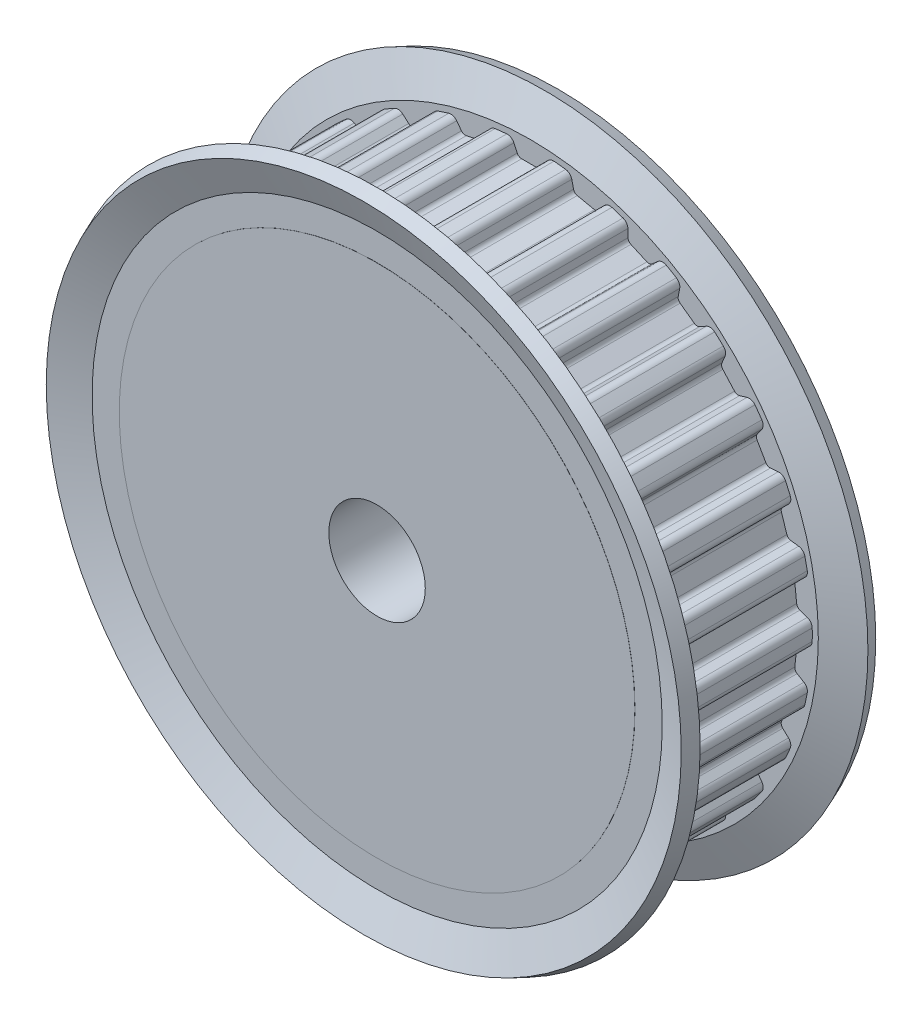
SolidWorks part; units mm, degrees
ref_plane "Front Plane" through (0, 0, 0) normal (0, 0, 1) x (1, 0, 0)
ref_plane "Top Plane" through (0, 0, 0) normal (0, 1, 0) x (1, 0, 0)
ref_plane "Right Plane" through (0, 0, 0) normal (1, 0, 0) x (0, 0, -1)
ref_axis "Axis1" through (0, 0, 55) along (0, 0, -1)
sketch "SketchRevolveGearBelt01" plane through (0, 0, 0) normal (1, 0, 0) x (0, 0, -1)
  line L0 (0, 0) -> (1, 0) construction
  line L1 (6.96, 0) -> (6.96, 21.3732)
  line L2 (6.96, 21.3732) -> (6.95, 21.3732)
  line L3 (6.95, 21.3732) -> (6.95, 23.6345)
  line L4 (6.95, 23.6345) -> (8.0633, 26.3223)
  line L5 (8.0633, 26.3223) -> (6.9547, 26.7815)
  line L6 (6.9547, 26.7815) -> (5.75, 23.8732)
  line L7 (5.75, 23.8732) -> (5.75, 23.3732)
  line L8 (5.75, 23.3732) -> (-5.75, 23.3732)
  line L9 (-5.75, 23.3732) -> (-5.75, 23.8732)
  line L10 (-5.75, 23.8732) -> (-6.9547, 26.7815)
  line L11 (-6.9547, 26.7815) -> (-8.0633, 26.3223)
  line L12 (-8.0633, 26.3223) -> (-6.95, 23.6345)
  line L13 (-6.95, 23.6345) -> (-6.95, 21.3732)
  line L14 (-6.95, 21.3732) -> (-6.96, 21.3732)
  line L15 (-6.96, 21.3732) -> (-6.96, 0)
  line L16 (-6.96, 0) -> (6.96, 0)
  dimension "GearBeltSide1" = 6.96
  dimension "GearBeltFlange1OutsideWidth" = 6.95
  dimension "GearBeltFlange1OutsideLength" = 2.2613
  dimension "GearBeltFlange1X" = 1.1133
  dimension "GearBeltFlange1Y" = 2.6878
  dimension "GearBeltFlangeThickness" = 1.2
  dimension "GearBeltToothWidth1" = 5.75
  dimension "GearBeltFlangeInside" = 0.5
  dimension "GearBeltOutsideDiameter" = 23.3732
  dimension "GearBeltToothWidth2" = 5.75
  dimension "GearBeltFlange2X" = 1.1133
  dimension "GearBeltFlange2OutsideWidth" = 6.95
revolve "GearBelt01" add sketch "SketchRevolveGearBelt01" angle 360 about L0
sketch "SketchToothGearBelt01" plane through (0, 0, 0) normal (0, 0, 1) x (1, 0, 0)
  line L0 (-1.3657, 22.9466) -> (-1.0894, 22.3542)
  line L1 (-0.7269, 22.1232) -> (0.7269, 22.1232)
  line L2 (1.0894, 22.3542) -> (1.3657, 22.9466)
  line L3 (1.9598, 23.2909) -> (0, 25.8309)
  line L4 (0, 25.8309) -> (-1.9598, 23.2909)
  arc A0 (-1.9598, 23.2909) -> (-1.3657, 22.9466) centre (-1.9095, 22.693) cw
  arc A1 (-1.0894, 22.3542) -> (-0.7269, 22.1232) centre (-0.7269, 22.5232) ccw
  arc A2 (0.7269, 22.1232) -> (1.0894, 22.3542) centre (0.7269, 22.5232) ccw
  arc A3 (1.3657, 22.9466) -> (1.9598, 23.2909) centre (1.9095, 22.693) cw
  dimension "GearBeltToothR1" = 1.2
  dimension "GearBeltToothR2" = 0.8
  dimension "GearBeltToothX1" = 0.2763
  dimension "GearBeltToothY1" = 0.5924
  dimension "GearBeltToothRootX" = 22.1232
  dimension "GearBeltToothRootY" = 22.1232
  dimension "GearBeltToothX2" = 0.2763
  dimension "GearBeltToothY2" = 0.5924
  dimension "GearBeltToothCapX1" = 1.9598
  dimension "GearBeltToothCapY1" = 2.54
  dimension "GearBeltToothCapX2" = 1.9598
  dimension "GearBeltToothCapY2" = 2.54
extrude "ToothExtrudeCutGearBelt01" cut sketch "SketchToothGearBelt01" against normal blind 5.75 and the other way blind 5.75
pattern_circular "PatternGearBelt01" count 30 every 12 about axis through (0, 0, 55) along (0, 0, -1) of "ToothExtrudeCutGearBelt01"
sketch "BoreRevolveSketch" plane through (0, 0, 0) normal (1, 0, 0) x (0, 0, -1)
  line L0 (0, 0) -> (1, 0) construction
  line L1 (-6.96, 0) -> (6.96, 0)
  line L2 (6.96, 0) -> (6.96, 4)
  line L3 (6.96, 4) -> (-6.96, 4)
  line L4 (-6.96, 4) -> (-6.96, 0)
  dimension "BoreSide1" = 6.96
  dimension "TaperSide1" = 4
  dimension "BoreSide2" = 6.96
  dimension "TaperSide2" = 4
revolve "BoreRevolveCut" cut sketch "BoreRevolveSketch" angle 360 about L0
sketch "AuxiliarySketchGearBelt01" plane through (0, 0, 0) normal (0, 0, 1) x (1, 0, 0)
  circle A0 centre (0, 0) radius 23.8732 construction
  dimension "PitchDiameter" = 47.7465
